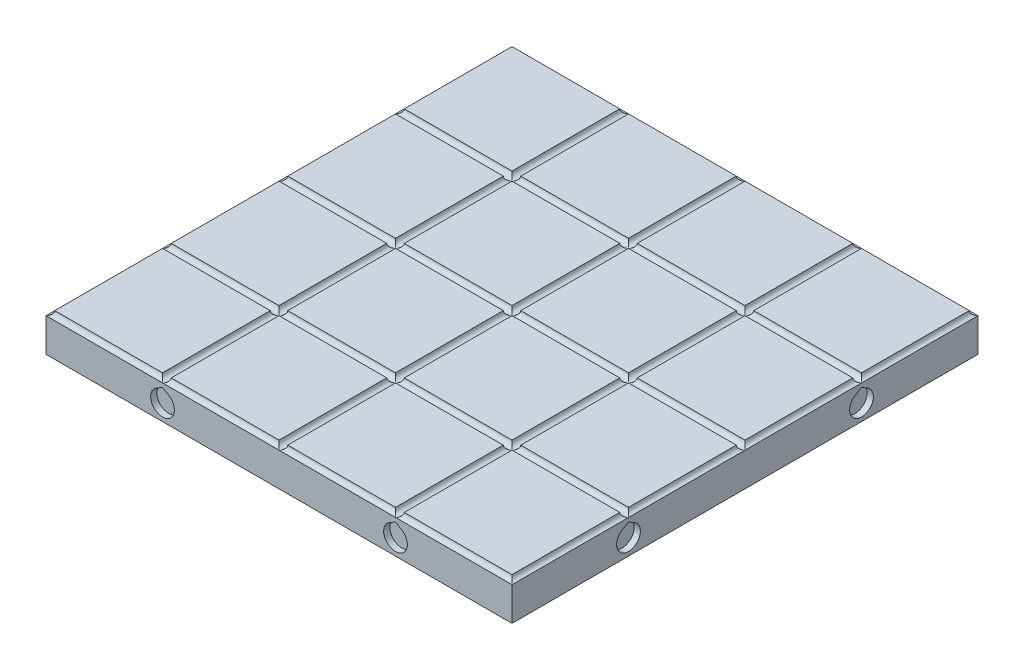
SolidWorks part; units mm, degrees
ref_plane "Спереди" through (0, 0, 0) normal (0, 0, 1) x (1, 0, 0)
ref_plane "Сверху" through (0, 0, 0) normal (0, 1, 0) x (1, 0, 0)
ref_plane "Справа" through (0, 0, 0) normal (1, 0, 0) x (0, 0, -1)
sketch "Эскиз1" plane through (0, 0, 0) normal (0, 1, 0) x (1, 0, 0)
  line L1 (80, -80) -> (-80, -80)
  line L2 (80, -80) -> (80, 80)
  line L3 (80, 80) -> (-80, 80)
  line L4 (-80, -80) -> (-80, 80)
  line L5 (0, 80) -> (0, -80) construction
  line L6 (80, 0) -> (-80, 0) construction
  point P0 (0, 0)
  dimension "D1" = 160
extrude "Бобышка-Вытянуть1" add sketch "Эскиз1" against normal blind 13
sketch "Эскиз2" plane through (0, 0, 0) normal (0, 1, 0) x (1, 0, 0)
  line L0 (-80, 80) -> (-80, -80)
sweep "Вырез-По траектории1" cut path "Эскиз2" circular profile diameter 3 parameters "D3"=3
pattern_linear "Линейный массив1" count 5 spacing 40 along (1, 0, 0) of "Вырез-По траектории1"
sketch "Эскиз180" plane through (0, 0, 0) normal (0, 1, 0) x (1, 0, 0)
  line L0 (-80, -80) -> (80, -80)
sweep "Вырез-По траектории2" cut path "Эскиз180" circular profile diameter 3 parameters "D3"=3
pattern_linear "Линейный массив2" count 5 spacing 40 along (1, 0, 0) count 5 spacing 40 along (0, 0, -1) of "Вырез-По траектории2"
sketch "Эскиз181" plane through (0, 0, 80) normal (0, 0, 1) x (1, 0, 0)
  line L0 (0, 22.1626) -> (0, -39.4564) construction
  line L3 (-40, -1.5) -> (-40, -13) construction
  line L4 (-80, -13) -> (80, -13) construction
  line L5 (40, -2.8598) -> (37.9625, -4.0361)
  line L8 (40, -2.8598) -> (42.0375, -4.0361)
  line L10 (-48.6563, -7.25) -> (-30.5924, -7.25) construction
  line L13 (-40, -2.8598) -> (-42.0375, -4.0361)
  line L14 (-80, -1.5) -> (-40, -1.5) construction
  line L15 (-40, -2.8598) -> (-37.9625, -4.0361)
  circle A2 centre (-40, -7.5652) radius 4.075
  circle A3 centre (40, -7.5652) radius 4.075
  point P5 (0, 0)
  point P6 (0, 0)
  point P14 (0, 0)
  point P15 (0, 0)
  point P16 (0, 0)
  point P18 (-40, -2.3603)
  point P21 (0, 0)
  point P22 (-40, -11.6402)
  point P23 (0, 0)
  point P24 (0, 0)
  point P26 (-38.109, -3.4535)
  point P27 (0, 0)
  point P29 (0, 0)
  point P30 (-40, -2.1962)
  point P31 (-37.9292, -3.5686)
  point P37 (-42.0375, -3.5361)
  point P38 (0, 0)
  point P39 (-37.9625, -4.0361)
  point P40 (-37.9625, -4.0361)
  point P41 (0, 0)
  point P42 (0, 0)
  point P43 (0, 0)
  dimension "D1" = 8.15
  dimension "D2" = 60
  dimension "D3" = 1.3598
  dimension "D4" = 1.3598
  dimension "D5" = 120
extrude "Вырез-Вытянуть1" cut sketch "Эскиз181" against normal blind 2.15 contours A2 | A2 L15 L13 | A3 | L5 A3 L8
pattern_circular "Круговой массив1" count 4 over 360 about axis through (0, -13, 0) along (0, -1, 0) of "Вырез-Вытянуть1" other way count 4
